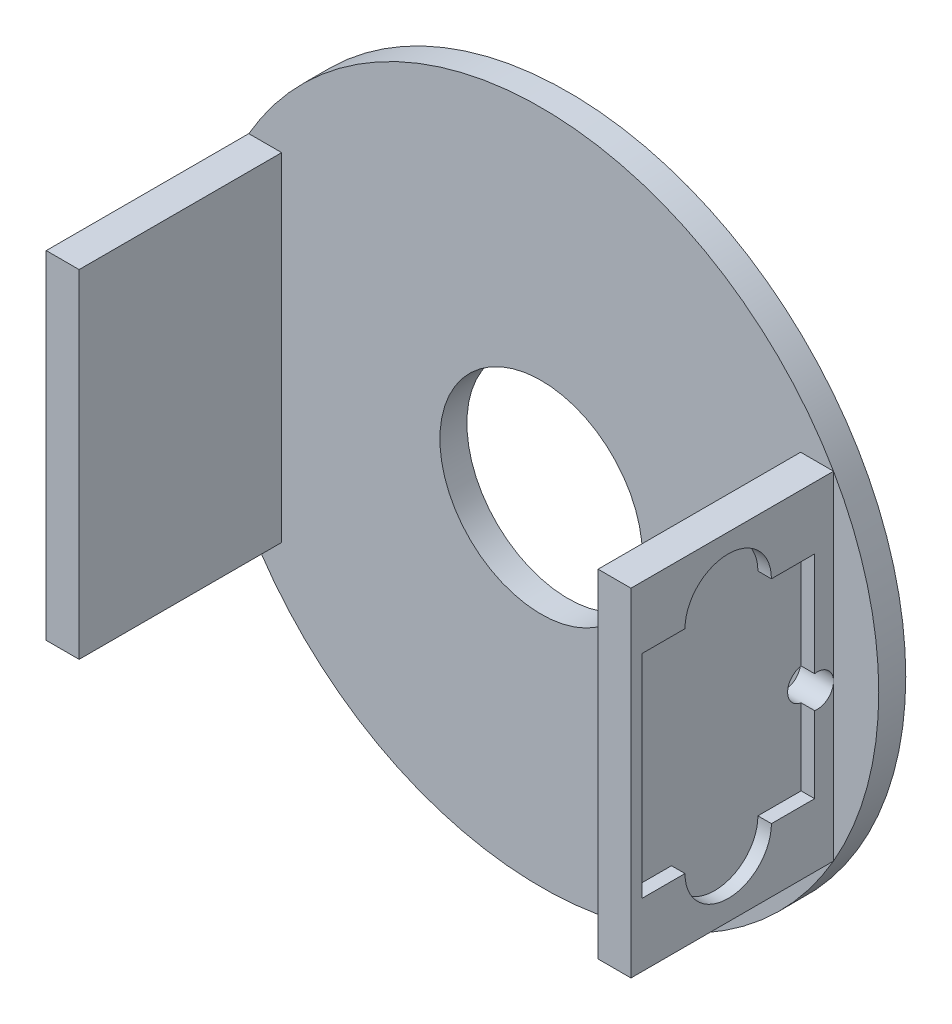
SolidWorks part; units mm, degrees
ref_plane "Front Plane" through (0, 0, 0) normal (1, 0, 0) x (0, 1, 0)
ref_plane "Top Plane" through (0, 0, 0) normal (0, 0, 1) x (0, 1, 0)
ref_plane "Right Plane" through (0, 0, 0) normal (0, 1, 0) x (-1, 0, 0)
sketch "Sketch1" plane through (0, 0, 0) normal (0, 0, 1) x (0, 1, 0)
  circle A0 centre (0, 0) radius 25
  circle A1 centre (0, 0) radius 7.5
  dimension "D1" = 50
  dimension "D2" = 15
extrude "Boss-Extrude1" add sketch "Sketch1" along normal blind 2
sketch "Sketch3" plane through (0, 0, 2) normal (0, 0, 1) x (1, 0, 0)
  line L0 (0, 0) -> (52.2678, 0) construction
  line L1 (0, 0) -> (-54.0938, 0) construction
  line L2 (0, 0) -> (0, -25) construction
  line L3 (21.6506, 12.5) -> (19.2145, 12.5)
  line L4 (21.6506, 12.5) -> (21.6506, -12.5)
  line L5 (21.6506, -12.5) -> (19.2145, -12.5)
  line L6 (19.2145, 12.5) -> (19.2145, -12.5)
  line L7 (-21.6506, -12.5) -> (-19.2145, -12.5)
  line L8 (-19.2145, 12.5) -> (-19.2145, -12.5)
  line L9 (-21.6506, 12.5) -> (-19.2145, 12.5)
  line L10 (-21.6506, 12.5) -> (-21.6506, -12.5)
  circle A0 centre (0, 0) radius 25 construction
  dimension "D1" = 25
extrude "Boss-Extrude2" add sketch "Sketch3" along normal blind 15 contours L9 L8 L7 L10
extrude "Boss-Extrude3" add sketch "Sketch3<3>" along normal blind 15
sketch "Sketch3<3>" plane through (0, 0, 2) normal (0, 0, 1) x (1, 0, 0) same geometry as "Sketch3"
sketch "Sketch8" plane through (21.6506, 0, 0) normal (1, 0, 0) x (0, 1, 0)
  line L1 (-8.8185, 16) -> (6.8815, 16)
  line L2 (-8.8185, 16) -> (-8.8185, 3.2)
  line L3 (-8.8185, 3.2) -> (6.8815, 3.2)
  line L4 (6.8815, 16) -> (6.8815, 3.2)
  line L5 (-12.5, 17) -> (12.5, 17) construction
  dimension "D1" = 15.7
  dimension "D2" = 12.8
  dimension "D3" = 1
sketch "Sketch9" plane through (21.6506, 0, 0) normal (1, 0, 0) x (0, 1, 0)
  line L0 (-12.5, 17) -> (-12.5, 2) construction
  line L1 (-7.8, 16.2) -> (7.9, 16.2)
  line L2 (-7.8, 16.2) -> (-7.8, 13)
  line L3 (-7.8, 3.4) -> (7.9, 3.4)
  line L4 (7.9, 16.2) -> (7.9, 13)
  line L5 (12.5, 17) -> (12.5, 2) construction
  line L6 (-12.5, 2) -> (12.5, 2) construction
  line L7 (7.9, 6.6) -> (7.9, 3.4)
  line L8 (-7.8, 6.6) -> (-7.8, 3.4)
  arc A0 (7.9, 6.6) -> (7.9, 13) centre (7.9, 9.8) ccw
  arc A1 (-7.8, 13) -> (-7.8, 6.6) centre (-7.8, 9.8) ccw
  dimension "D6" = 6.4
  dimension "D7" = 6.4
  dimension "D1" = 12.8
  dimension "D2" = 15.7
  dimension "D3" = 4.7
  dimension "D4" = 4.6
  dimension "D5" = 1.4
extrude "Cut-Extrude3" cut sketch "Sketch9" against normal blind 1
sketch "Sketch10" plane through (21.6506, 0, 0) normal (1, 0, 0) x (0, 1, 0)
  line L0 (-8.8185, 3.2) -> (6.8815, 3.2) construction
  circle A0 centre (-0.9685, 3.2) radius 1.2
extrude "Cut-Extrude4" cut sketch "Sketch10" against normal blind 9
